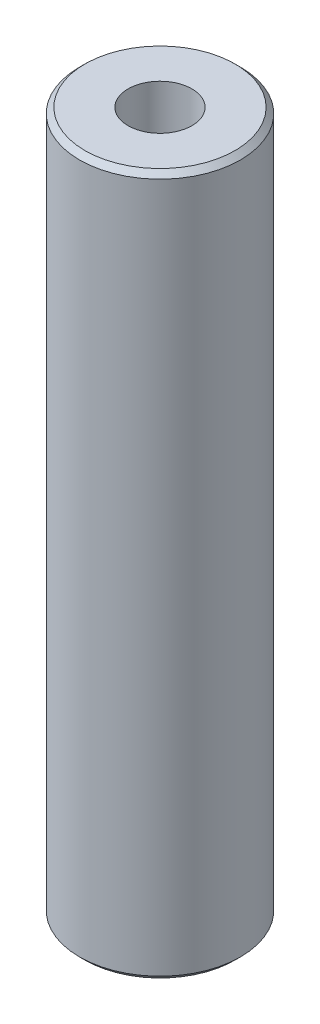
SolidWorks part; units mm, degrees
ref_plane "Front Plane" through (0, 0, 0) normal (0, 0, 1) x (1, 0, 0)
ref_plane "Top Plane" through (0, 0, 0) normal (0, 1, 0) x (1, 0, 0)
ref_plane "Right Plane" through (0, 0, 0) normal (1, 0, 0) x (0, 0, -1)
sketch "Sketch1" plane through (0, 0, 0) normal (0, 1, 0) x (1, 0, 0)
  circle A0 centre (0, 0) radius 60
  dimension "SHAFT_OD" = 120
extrude "Boss-Extrude1" add sketch "Sketch1" along normal blind 522.7859
sketch "Sketch2" plane through (0, 0, 0) normal (0, 1, 0) x (1, 0, 0)
  circle A0 centre (0, 0) radius 23.8124
  dimension "BORE_D" = 47.6247
extrude "Cut-Extrude1" cut sketch "Sketch2" along normal through all
chamfer "Chamfer1" distance 4.0308 angle 45 2 edges at (0, 522.7859, 60) (0, 0, 60)
